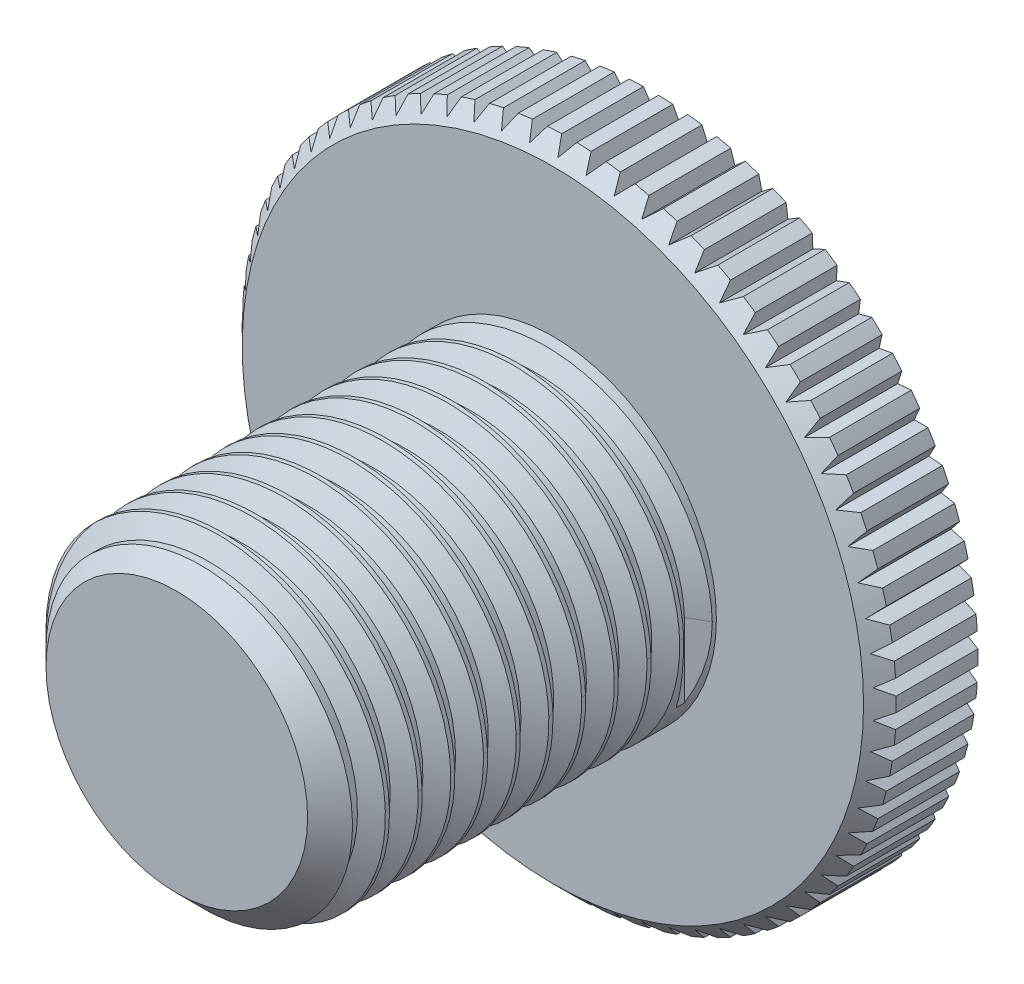
SolidWorks part; units mm, degrees
ref_plane "Спереди XY" through (0, 0, 0) normal (0, 0, 1) x (1, 0, 0)
ref_plane "Сверху XZ" through (0, 0, 0) normal (0, 1, 0) x (1, 0, 0)
ref_plane "Справа ZY" through (0, 0, 0) normal (1, 0, 0) x (0, 0, -1)
sketch "Эскиз1" plane through (0, 0, 0) normal (0, 0, 1) x (1, 0, 0)
  circle A0 centre (0, 0) radius 20
  dimension "D1" = 40
extrude "Бобышка-Вытянуть1" add sketch "Эскиз1" along normal blind 6
sketch "Эскиз2" plane through (0, 0, 6) normal (0, 0, 1) x (1, 0, 0)
  circle A0 centre (0, 0) radius 10
  dimension "D1" = 20
extrude "Бобышка-Вытянуть2" add sketch "Эскиз2" along normal blind 23
chamfer "Фаска1" distance 2 angle 45 1 edges at (10, 0, 29)
thread "Резьба1" pitch 2 method cut profile "Профиль резьбы1" start angle 0, offset 4, length 23, pitch 2, diameter 20
ref_plane "Плоскость1" through (-10, 0, 31) normal (0, -1, 0) x (-1, 0, 0)
sketch "Профиль резьбы1" plane through (-10, 0, 31) normal (0, -1, 0) x (-1, 0, 0)
  line L0 (0, 0) -> (0, 2) construction
  line L11 (0, 0) -> (0, 1.75)
  line L12 (0, 1.75) -> (-1.0825, 1.125)
  line L13 (-1.0825, 1.125) -> (-1.0825, 0.625)
  line L15 (-1.0825, 0.625) -> (0, 0)
  line L17 (-1.0825, 0.875) -> (0, 0.875) construction
  point P2 (0, 0)
  dimension "Pitch" = 2
  dimension "Profile_Angle" = 60
  dimension "Profile_Land" = 0.5
  dimension "Profile_Height" = 1.0825
chamfer "Фаска2" distance 1 angle 45 1 edges at (20, 0, 6)
sketch "Эскиз9" plane through (0, 0, 0) normal (0, 0, -1) x (-1, 0, 0)
  line L0 (0, 17.6031) -> (0, 21.57) construction
  line L1 (0, 19.3) -> (1.46, 21.5038)
  line L2 (0, 19.3) -> (-1.46, 21.5038)
  line L3 (-1.46, 21.5038) -> (1.46, 21.5038)
  dimension "D1" = 19.3
extrude "Вырез-Вытянуть3" cut sketch "Эскиз9" against normal blind 10
pattern_circular "Круговой массив1" count 70 over 360 about axis through (0, 0, 0) along (0, 0, 1) of "Вырез-Вытянуть3"
sketch "Эскиз12" plane through (0, 0, 0) normal (0, 1, 0) x (1, 0, 0)
  line L0 (10, -8) -> (8.9175, -7.375)
  line L1 (8.9175, -7.375) -> (8.9175, -6.875)
  line L2 (8.9175, -6.875) -> (10, -6.25)
  line L3 (10, -6.25) -> (10, -8)
extrude "Вырез-Вытянуть10" cut sketch "Эскиз12" against normal blind 10
